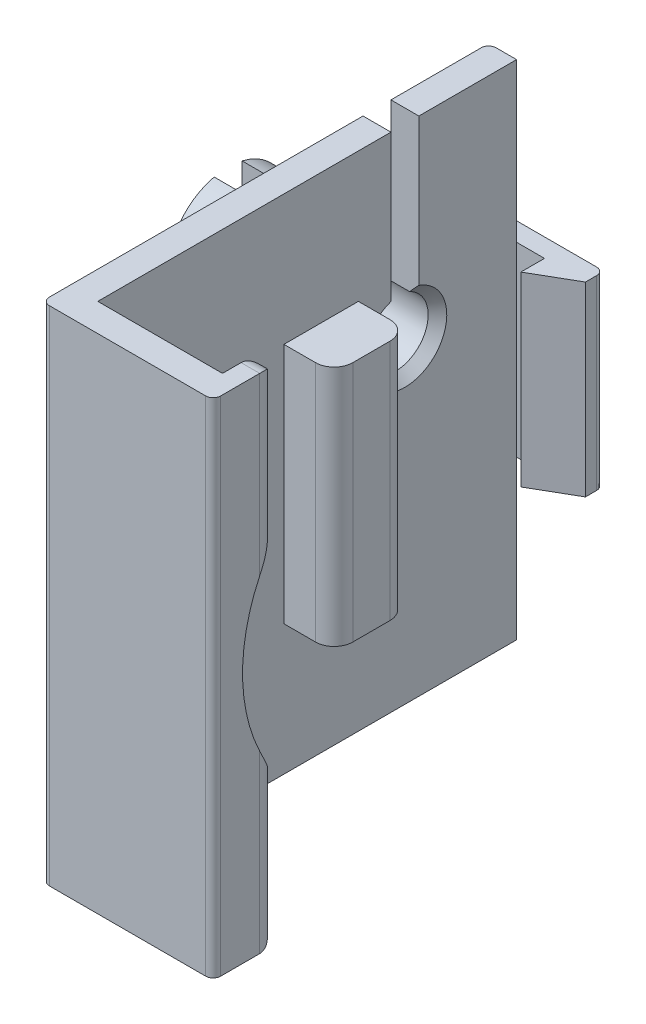
SolidWorks part; units mm, degrees
ref_plane "Front Plane" through (0, 0, 0) normal (0, 0, 1) x (1, 0, 0)
ref_plane "Top Plane" through (0, 0, 0) normal (0, 1, 0) x (1, 0, 0)
ref_plane "Right Plane" through (0, 0, 0) normal (1, 0, 0) x (0, 0, -1)
sketch "Sketch1" plane through (0, 0, 0) normal (0, 1, 0) x (1, 0, 0)
  line L0 (0, 0) -> (-2.2, 0)
  line L5 (-2.2, 0) -> (-2.2, -1.2702)
  line L6 (-2.2, -1.2702) -> (0, 0)
  dimension "D1" = 60
  dimension "D2" = 2.2
extrude "Boss-Extrude1" add sketch "Sketch1" along normal blind 5 and the other way blind 5
sketch "Sketch2" plane through (0, 0, 0) normal (0, 0, -1) x (-1, 0, 0)
  line L0 (0, 5) -> (2.2, 5) construction
  line L1 (0, -5) -> (3.7, -5)
  line L2 (0, -5) -> (0, 5)
  line L3 (0, 5) -> (3.7, 5)
  line L4 (3.7, -5) -> (3.7, 5)
  line L5 (0, -5) -> (3.7, 5) construction
  line L6 (0, 5) -> (3.7, -5) construction
  line L7 (2.2, -5) -> (2.2, 5) construction
  point P4 (1.85, 0)
  dimension "D1" = 1.5
extrude "Boss-Extrude2" add sketch "Sketch2" along normal blind 1
sketch "Sketch3" plane through (-3.7, 0, 0) normal (-1, 0, 0) x (0, 0, 1)
  line L0 (0, 0) -> (12.5427, 0) construction
  line L1 (0, -13.5) -> (22.5, -13.5)
  line L2 (0, -13.5) -> (0, 13.5)
  line L3 (0, 13.5) -> (22.5, 13.5)
  line L4 (22.5, -13.5) -> (22.5, 13.5)
  line L5 (0, -13.5) -> (22.5, 13.5) construction
  line L6 (0, 13.5) -> (22.5, -13.5) construction
  line L7 (0, -5) -> (0, 5) construction
  line L9 (0, 5) -> (-1, 5)
  line L10 (0, 5) -> (0, -5)
  line L11 (0, -5) -> (-1, -5)
  line L12 (-1, 5) -> (-1, -5)
  line L13 (0, 5) -> (-1, -5) construction
  line L14 (0, -5) -> (-1, 5) construction
  point P4 (11.25, 0)
  point P16 (-0.5, 0)
  line M6 (0, -5) -> (0, 5)
  line M7 (0, 5) -> (-1, 5)
  line M8 (-1, 5) -> (-1, -5)
  line M9 (-1, -5) -> (0, -5)
  dimension "D1" = 22.5
  dimension "D2" = 27
extrude "Boss-Extrude3" add sketch "Sketch3" along normal blind 1.5 contours L1 L4 L3 L2 M6 | M9 M6 M7 M8 region at (-3.7, 0, 11.25) region at (-3.7, 0, -0.5)
sketch "Sketch4" plane through (0, 0, 22.5) normal (0, 0, 1) x (1, 0, 0)
  line L0 (-4.45, 0) -> (4, 0) construction
  line L1 (-5.2, -13.5) -> (-3.7, -13.5)
  line L2 (-5.2, -13.5) -> (-5.2, 13.5)
  line L3 (-5.2, 13.5) -> (-3.7, 13.5)
  line L4 (-3.7, -13.5) -> (-3.7, 13.5)
  line L5 (-5.2, -13.5) -> (-3.7, 13.5) construction
  line L6 (-5.2, 13.5) -> (-3.7, -13.5) construction
  line L7 (-3.7, -13.5) -> (3, -13.5)
  line L8 (-3.7, -13.5) -> (-3.7, 13.5)
  line L9 (-3.7, 13.5) -> (3, 13.5)
  line L10 (3, -13.5) -> (3, 13.5)
  line L11 (-3.7, -13.5) -> (3, 13.5) construction
  line L12 (-3.7, 13.5) -> (3, -13.5) construction
  line L14 (3, 13.5) -> (4, 13.5)
  line L15 (3, 13.5) -> (3, -13.5)
  line L16 (3, -13.5) -> (4, -13.5)
  line L17 (4, 13.5) -> (4, -13.5)
  line L18 (3, 13.5) -> (4, -13.5) construction
  line L19 (3, -13.5) -> (4, 13.5) construction
  point P4 (-4.45, 0)
  point P11 (-0.35, 0)
  point P17 (3.5, 0)
  point P22 (0, 0)
  point P23 (0, 0)
  point P24 (0, 0)
  line M5 (-3.7, -13.5) -> (-3.7, 13.5)
  line M6 (-3.7, 13.5) -> (-5.2, 13.5)
  line M7 (-5.2, 13.5) -> (-5.2, -13.5)
  line M8 (-5.2, -13.5) -> (-3.7, -13.5)
  dimension "D2" = 6.7
  dimension "D3" = 1
extrude "Boss-Extrude4" add sketch "Sketch4" along normal blind 1.5 contours L7 L10 L9 M5 | M8 M5 M6 M7 region at (-4.45, 0, 22.5) region at (-0.35, 0, 22.5)
ref_plane "Plane1" through (0, 0, 0) normal (0, 1, 0) x (1, 0, 0)
sketch "Sketch5" plane through (-3.7, 0, 0) normal (1, 0, 0) x (0, 0, -1)
  line L5 (-10.5, -13.5) -> (-10.5, 13.5) construction
  line L7 (-12.5, 6.5) -> (-8.5, 6.5)
  line L8 (-12.5, 6.5) -> (-12.5, -6.5)
  line L9 (-12.5, -6.5) -> (-8.5, -6.5)
  line L10 (-8.5, 6.5) -> (-8.5, -6.5)
  line L11 (-12.5, 6.5) -> (-8.5, -6.5) construction
  line L12 (-12.5, -6.5) -> (-8.5, 6.5) construction
  line L14 (0, 13.5) -> (-22.5, 13.5) construction
  line L15 (0, 5) -> (0, 13.5) construction
  line L17 (0, -13.5) -> (-22.5, -13.5) construction
  point P6 (-10.5, 0)
  point P7 (-10.5, 0)
  point P12 (-10.5, 0)
  dimension "D1" = 13
  dimension "D2" = 4
  dimension "D3" = 10.5
extrude "Boss-Extrude5" add sketch "Sketch5" along normal blind 2.7 contours L8 L7 L10 L9
sketch "Sketch7" plane through (-3.7, 0, 0) normal (1, 0, 0) x (0, 0, -1)
  line L0 (0, 5) -> (0, 13.5) construction
  line L1 (0, 13.5) -> (-22.5, 13.5) construction
  line L2 (-6, 3.5) -> (-6, 13.5) construction
  line L3 (-6.75, 13.5) -> (-6.75, 5.0811)
  line L4 (-5.25, 13.5) -> (-5.25, 5.0811)
  line L5 (-6.75, 13.5) -> (-5.25, 13.5)
  circle A0 centre (-6, 3.5) radius 1.75
  circle A1 centre (-6, 3.5) radius 3.25
  line M6 (0, 13.5) -> (-22.5, 13.5)
  line M12 (-8.5, 6.5) -> (-8.5, -6.5)
  dimension "D1" = 3.5
  dimension "D6" = 1.5
  dimension "D2" = 6
  dimension "D3" = 10
  dimension "D4" = 0.75
  dimension "D5" = 1.5
extrude "Cut-Extrude1" cut sketch "Sketch7" against normal through all contours A0 | A1 L2 L5 L3 | L2 A1 L4 M6 | L2 A0 L4 A1 | A0 L2 A1 L3 region at (-3.7, 5.9573, 6.3783) region at (-3.7, 5.9573, 5.6217) region at (-3.7, 5.159, 5.6265) region at (-3.7, 10.1104, 6.3758) region at (-3.7, 10.1104, 5.6242)
extrude "Boss-Extrude6" add sketch "Sketch7<3>" against normal blind 8 from surface contours A1 M12 | L3 A1 L4 A0 M12 region at (-3.7, 5.8717, 6.8361) region at (-3.7, 3.5, 8.8032) starting at face at (-5.2, 2.8193, 5.8333)
sketch "Sketch7<3>" plane through (-3.7, 0, 0) normal (1, 0, 0) x (0, 0, -1) same geometry as "Sketch7"
ref_plane "Plane2" through (0, 0.25, 0) normal (0, -1, 0) x (-1, 0, 0)
sketch "Sketch8" plane through (0, 0.25, 0) normal (0, -1, 0) x (-1, 0, 0)
  line L0 (13.2, -2.75) -> (5.2, -2.75) construction
  line L1 (13.2, -2.75) -> (8.4, -2.75)
  line L2 (13.2, -2.75) -> (13.2, -9.25)
  line L3 (13.2, -9.25) -> (8.4, -9.25)
  line L4 (8.4, -2.75) -> (8.4, -9.25)
  line L5 (13.2, -2.75) -> (8.4, -9.25) construction
  line L6 (13.2, -9.25) -> (8.4, -2.75) construction
  line L7 (13.2, -9.25) -> (13.2, -2.75) construction
  point P4 (10.8, -6)
  dimension "D1" = 4.8
ref_axis "Axis1" through (-13.2, 3.5, 6) along (1, 0, 0)
ref_plane "Plane3" through (0, 3.5, 0) normal (0, 1, 0) x (1, 0, 0)
extrude "Cut-Extrude2" cut sketch "Sketch8" against normal up to surface (3.25 mm away) up to plane "Plane3"
fillet "Fillet4" radius 1 2 edges at (-1, 0, 12.5) (-1, 0, 8.5)
chamfer "Chamfer1" distance 2 angle 45 2 edges at (-8.4, 3.5, 8.5) (-8.4, 3.5, 3.5)
chamfer "Chamfer3" distance 0.5 angle 45 1 edges at (-3.7, 1.75, 6)
extrude "Boss-Extrude7" add sketch "Sketch4<3>" against normal blind 2 separate body contours L17 L10 L16 | L17 L14 L10 region at (3.5, 0, 22.5)
sketch "Sketch4<3>" plane through (0, 0, 22.5) normal (0, 0, 1) x (1, 0, 0) same geometry as "Sketch4"
extrude "Boss-Extrude8" add sketch "Sketch4<4>" along normal up to surface (1.5 mm away) contours L17 L15 | L17 L10 L16 | L17 L14 L10 region at (3.5, 0, 22.5) up to face at (-1.1, 0, 24)
sketch "Sketch4<4>" plane through (0, 0, 22.5) normal (0, 0, 1) x (1, 0, 0) same geometry as "Sketch4"
fillet "Fillet6" radius 1 4 edges at (3, 0, 20.5) (3.5, -13.5, 20.5) (4, 0, 20.5) (3.5, 13.5, 20.5)
fillet "Fillet8" radius 0.4 6 edges at (0, 0, -1) (-5.2, -9.25, 0) (-5.2, 9.25, 0) (-5.2, 0, -1) (-5.2, 0, 24) (4, 0, 24)
sketch "Sketch9" plane through (3, 0, 0) normal (-1, 0, 0) x (0, 0, 1)
  line L0 (0, 0) -> (16.2153, 0) construction
  circle A0 centre (12.9213, 0) radius 9.5
  point P2 (0, 0)
  point P3 (10.1205, 0)
  point P7 (0, 0)
  point P8 (10.6389, 0)
  point P9 (12.7629, 0)
  point P10 (12.9213, 0)
  dimension "D1" = 19
extrude "Cut-Extrude3" cut sketch "Sketch9" against normal through all
equation "\"WallThick\"= 1.2'thickness of wall for printer"
equation "\"dHole\"= 3.3'diameter of screw hole"
equation "\"dCable\"= 1.5"
equation "\"FillHole\"= 8'Height of fill hole to seal with hot glue"
equation "\"D1@Sketch8\"=0.6*\"FillHole\""
equation "\"D1@Boss-Extrude6\"=\"FillHole\""
